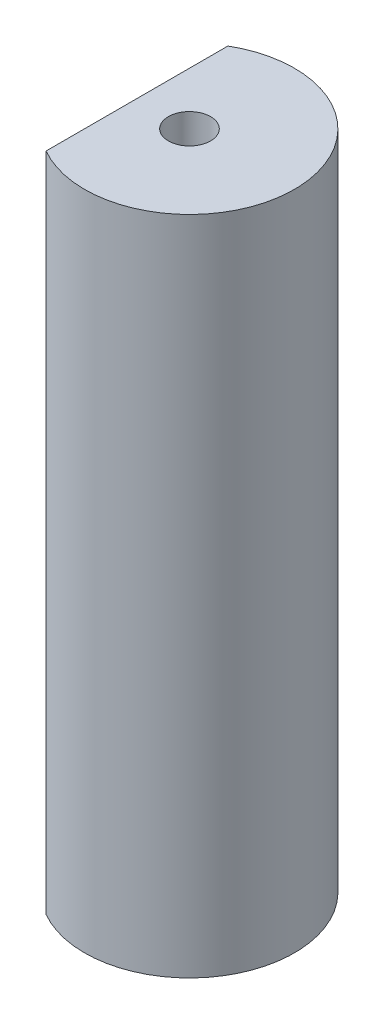
SolidWorks part; units mm, degrees
material "Delrin 2700 NC010, Low Viscosity Acetal Copolymer (SS)"
ref_plane "Front Plane" through (0, 0, 0) normal (0, 0, 1) x (1, 0, 0)
ref_plane "Top Plane" through (0, 0, 0) normal (0, 1, 0) x (1, 0, 0)
ref_plane "Right Plane" through (0, 0, 0) normal (1, 0, 0) x (0, 0, -1)
sketch "Sketch1" plane through (0, 0, 0) normal (0, 1, 0) x (1, 0, 0)
  circle A0 centre (0, 0) radius 12.7
  dimension "D1" = 25.4
extrude "Boss-Extrude1" add sketch "Sketch1" along normal blind 80
sketch "Sketch2" plane through (0, 0, 0) normal (0, -1, 0) x (1, 0, 0)
  point P0 (0, 0)
hole_wizard "Tap Drill for 1/4-20 Tap1" positions "Sketch2" profile "Sketch3" hole size "1/4-20" standard "ANSI Inch"
sketch "Sketch3" plane through (0, 0, 0) normal (1, 0, 0) x (0, 0, -1)
  line L0 (0, 0) -> (0, 11.6938)
  line L1 (0, 11.6938) -> (2.5527, 10.16)
  line L2 (2.5527, 10.16) -> (2.5527, 0)
  line L5 (2.5527, 0) -> (0, 0)
  line L10 (0, 11.6938) -> (-2.5527, 10.16) construction
  line L11 (0, -6.35) -> (0, 107.95) construction
  dimension "Hole Dia." = 5.1054
  dimension "Hole Depth" = 10.16
  dimension "Drill Angle" = 118
sketch "Sketch4" plane through (0, 80, 0) normal (0, 1, 0) x (1, 0, 0)
  point P0 (0, 0)
hole_wizard "Tap Drill for 1/4-20 Tap2" positions "Sketch4" profile "Sketch5" hole size "1/4-20" standard "ANSI Inch"
sketch "Sketch5" plane through (0, 80, 0) normal (1, 0, 0) x (0, 0, 1)
  line L0 (0, 0) -> (0, 11.6938)
  line L1 (0, 11.6938) -> (2.5527, 10.16)
  line L2 (2.5527, 10.16) -> (2.5527, 0)
  line L5 (2.5527, 0) -> (0, 0)
  line L10 (0, 11.6938) -> (-2.5527, 10.16) construction
  line L11 (0, -6.35) -> (0, 107.95) construction
  dimension "Hole Dia." = 5.1054
  dimension "Hole Depth" = 10.16
  dimension "Drill Angle" = 118
sketch "Sketch6" plane through (0, 80, 0) normal (0, 1, 0) x (1, 0, 0)
  line L0 (-6.35, 10.9985) -> (-6.35, -10.9985)
  circle A0 centre (0, 0) radius 12.7 construction
  arc A2 (-6.35, 10.9985) -> (-6.35, -10.9985) centre (0, 0) ccw
  point P4 (-12.7, 0)
  point P5 (-12.7, 0)
  point P6 (-12.54, 2.0094)
  dimension "D1" = 6.35
extrude "Cut-Extrude1" cut sketch "Sketch6" against normal through all
